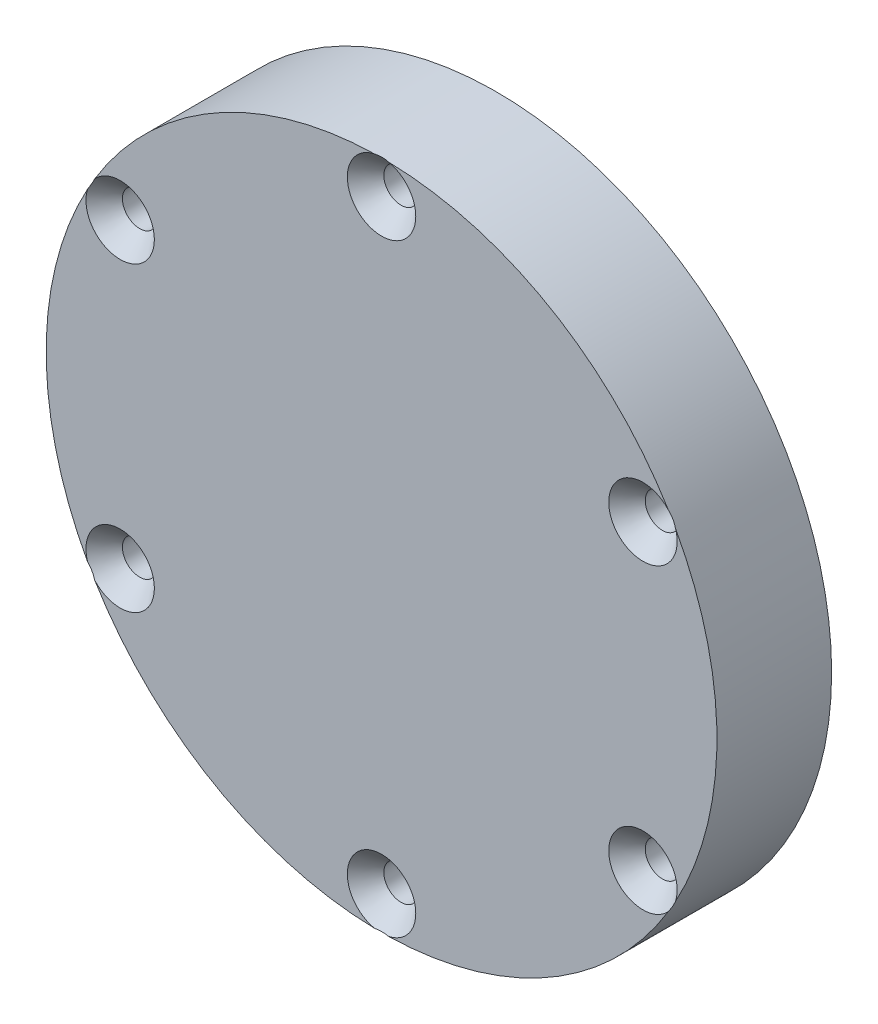
SolidWorks part; units mm, degrees
material "6061-T6 (SS)"
ref_plane "Front Plane" through (0, 0, 0) normal (0, 0, 1) x (1, 0, 0)
ref_plane "Top Plane" through (0, 0, 0) normal (0, 1, 0) x (1, 0, 0)
ref_plane "Right Plane" through (0, 0, 0) normal (1, 0, 0) x (0, 0, -1)
sketch "Sketch1" plane through (0, 0, 0) normal (0, 0, 1) x (1, 0, 0)
  circle A0 centre (0, 0) radius 31.75
  dimension "D1" = 63.5
extrude "Boss-Extrude1" add sketch "Sketch1" along normal blind 10.8585
hole_wizard "CSK for #4 Flat Head Socket Cap Screw1" positions "Sketch3" profile "Sketch2" countersink size "#4" standard "Ansi Inch" end condition through all
sketch "Sketch3" plane through (0, 0, 10.8585) normal (0, 0, 1) x (1, 0, 0)
  line L0 (0, 0) -> (0, 28.575) construction
  point P0 (0, 28.575)
  dimension "D1" = 28.575
sketch "Sketch2" plane through (0, 28.575, 10.8585) normal (1, 0, 0) x (0, -1, 0)
  line L0 (0, 0) -> (0, 10.8585)
  line L1 (0, 10.8585) -> (1.6319, 10.8585)
  line L2 (1.6319, 10.8585) -> (1.6319, 1.8481)
  line L3 (1.6319, 1.8481) -> (3.2385, 0)
  line L5 (3.2385, 0) -> (0, 0)
  line L6 (-1.6319, 1.8481) -> (-3.2385, 0) construction
  line L11 (0, -6.35) -> (0, 107.95) construction
  dimension "Thru Hole Dia." = 3.2639
  dimension "Thru Hole Depth" = 10.8585
  dimension "Near C'Sink Dia." = 6.477
  dimension "Near C'Sink Angle" = 82
pattern_circular "CirPattern1" count 6 over 360 about axis through (0, 0, 10.8585) along (0, 0, 1) of "CSK for #4 Flat Head Socket Cap Screw1"
sketch "Sketch4" plane through (0, 0, 0) normal (0, 0, -1) x (-1, 0, 0)
  circle A3 centre (0, 0) radius 29.3687
  arc A4 (-3.1585, 29.1984) -> (-23.7073, 17.3346) centre (0, 0) ccw
  arc A38 (23.7073, 17.3346) -> (26.8658, 11.8639) centre (24.7467, 14.2875) ccw
  circle A39 centre (0, 28.575) radius 3.2194
  arc A40 (-3.1585, 29.1984) -> (3.1585, 29.1984) centre (0, 28.575) ccw
  arc A41 (26.8658, -11.8639) -> (23.7073, -17.3346) centre (24.7467, -14.2875) ccw
  arc A42 (3.1585, -29.1984) -> (-3.1585, -29.1984) centre (0, -28.575) ccw
  arc A43 (-23.7073, -17.3346) -> (-26.8658, -11.8639) centre (-24.7467, -14.2875) ccw
  arc A44 (-26.8658, 11.8639) -> (-23.7073, 17.3346) centre (-24.7467, 14.2875) ccw
  arc A45 (23.7073, 17.3346) -> (3.1585, 29.1984) centre (0, 0) ccw
  arc A46 (26.8658, -11.8639) -> (26.8658, 11.8639) centre (0, 0) ccw
  arc A47 (3.1585, -29.1984) -> (23.7073, -17.3346) centre (0, 0) ccw
  arc A48 (-23.7073, -17.3346) -> (-3.1585, -29.1984) centre (0, 0) ccw
  arc A49 (-26.8658, 11.8639) -> (-26.8658, -11.8639) centre (0, 0) ccw
  dimension "D1" = 2.3813
  dimension "D2" = 1.5875
  dimension "D3" = 6
extrude "Cut-Extrude1" cut sketch "Sketch4" against normal blind 8.4772
fillet "Fillet1" radius 3.175 12 edges at (3.1585, 29.1984, 4.2386) (-3.1585, 29.1984, 4.2386) (-23.7073, 17.3346, 4.2386) (-26.8658, 11.8639, 4.2386) (-26.8658, -11.8639, 4.2386) (-23.7073, -17.3346, 4.2386) (-3.1585, -29.1984, 4.2386) (3.1585, -29.1984, 4.2386) (23.7073, -17.3346, 4.2386) (26.8658, -11.8639, 4.2386) (23.7073, 17.3346, 4.2386) (26.8658, 11.8639, 4.2386)
sketch "Sketch5" plane through (0, 0, 8.4772) normal (0, 0, -1) x (-1, 0, 0)
  circle A0 centre (0, 0) radius 4.7625
  dimension "D1" = 9.525
extrude "Cut-Extrude2" cut sketch "Sketch5" against normal blind 1.5875
